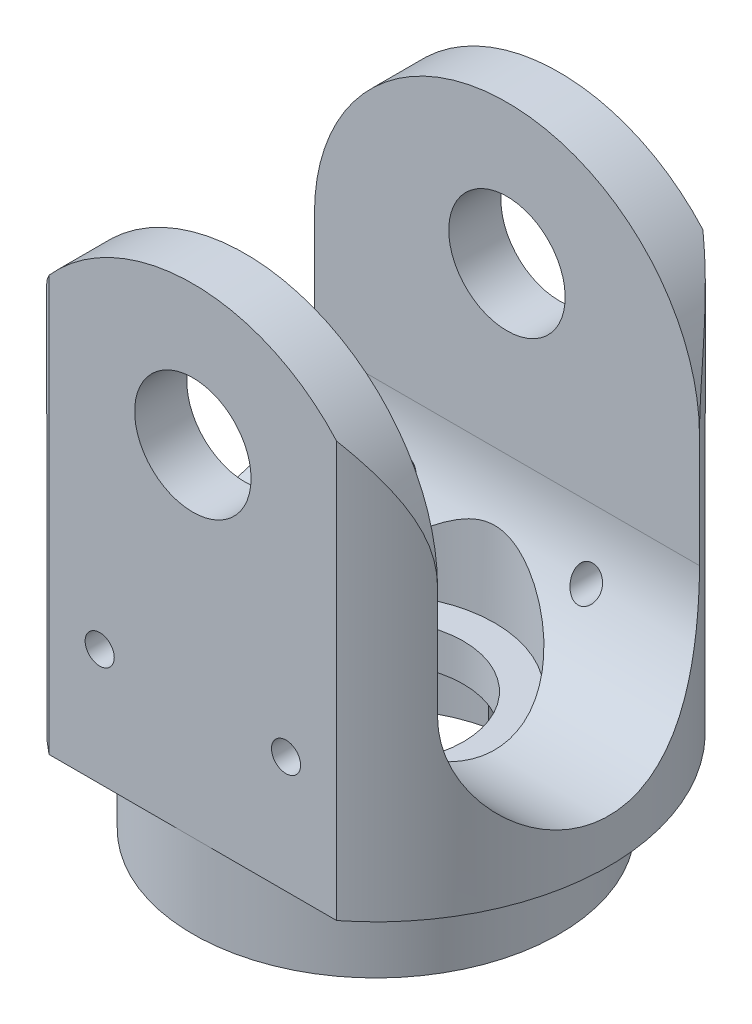
SolidWorks part; units mm, degrees
material "7075-T6 (SN)"
ref_plane "X-Y Datum" through (0, 0, 0) normal (0, 0, 1) x (1, 0, 0)
ref_plane "X-Z Datum" through (0, 0, 0) normal (0, 1, 0) x (1, 0, 0)
ref_plane "Y-Z Datum" through (0, 0, 0) normal (1, 0, 0) x (0, 0, -1)
sketch "Sketch1" plane through (0, 0, 0) normal (0, 1, 0) x (1, 0, 0)
  circle A0 centre (0, 0) radius 12.7
  dimension "D1" = 25.4
extrude "Boss-Extrude1" add sketch "Sketch1" along normal blind 15.367 and the other way blind 15.367
ref_plane "Plane2" through (0, 0, 9.9886) normal (0, 0, 1) x (1, 0, 0)
sketch "Sketch4" plane through (0, 0, 9.9886) normal (0, 0, 1) x (1, 0, 0)
  line L1 (-12.7, 15.367) -> (12.7, 15.367)
  line L2 (-12.7, 15.367) -> (-12.7, -15.367)
  line L3 (-12.7, -15.367) -> (12.7, -15.367)
  line L4 (12.7, 15.367) -> (12.7, -15.367)
extrude "Cut-Extrude2" cut sketch "Sketch4" along normal through all
mirror "Mirror2" about plane through (0, 0, 0) normal (0, 0, 1) of "Cut-Extrude2"
sketch "Sketch5" plane through (0, 0, 0) normal (1, 0, 0) x (0, 0, -1)
  line L0 (9.9886, 15.367) -> (-9.9886, 15.367) construction
  line L1 (-7.1437, 15.367) -> (7.1437, 15.367)
  line L2 (-7.1437, 15.367) -> (-7.1437, -1.27)
  line L3 (-7.1437, -1.27) -> (7.1438, -1.27)
  line L4 (7.1437, 15.367) -> (7.1438, -1.27)
  line L5 (0, 13.97) -> (0, -13.97) construction
  line L6 (0, -8.4138) -> (0, 15.367) construction
  arc A0 (-7.1437, -1.27) -> (7.1438, -1.27) centre (0, -1.27) ccw
  dimension "D3" = 16.637
  dimension "D4" = 23.7808
  dimension "D1" = 14.2875
  dimension "D2" = 7.1437
extrude "Cut-Extrude3" cut sketch "Sketch5" against normal through all both and the other way through all contours L6 A0 L3 | A0 L6 L3 | L2 L1 L4 L3 region at (0, -4.3019, 3.0319) region at (0, -4.3019, -3.0319)
sketch "Sketch6" plane through (0, 0, 9.9886) normal (0, 0, 1) x (1, 0, 0)
  line L0 (0, -43.0151) -> (0, 43.0151) construction
  line L1 (-7.8434, 15.367) -> (7.8434, 15.367) construction
  line L2 (10.5004, 4.8666) -> (14.8497, 4.8666)
  line L3 (-10.5004, 4.8666) -> (-14.8497, 4.8666)
  circle A0 centre (0, 4.8666) radius 10.5004
  arc A1 (14.8497, 4.8666) -> (-14.8497, 4.8666) centre (0, 4.8666) ccw
  line M2 (7.8434, 15.367) -> (-7.8434, 15.367)
  line M3 (-7.8434, 15.367) -> (-7.8434, -15.367)
  line M5 (7.8434, -15.367) -> (7.8434, 15.367)
  dimension "D1" = 21.0007
extrude "Cut-Extrude4" cut sketch "Sketch6" against normal through all contours L2 A1 L3 A0 M3 M2 M5 | A0 M2 M3 | A0 M5 M2 region at (10.124, 8.7197, 9.9886) region at (5.9543, 14.3505, 9.9886) region at (-5.9543, 14.3505, 9.9886)
sketch "Sketch7" plane through (0, -15.367, 0) normal (0, -1, 0) x (1, 0, 0)
  circle A0 centre (0, 0) radius 4.7625
  dimension "D1" = 9.525
extrude "Cut-Extrude5" cut sketch "Sketch7" against normal through all
sketch "Sketch9" plane through (0, -15.367, 0) normal (0, -1, 0) x (1, 0, 0)
  circle A0 centre (0, 0) radius 9.9822
  circle A1 centre (0, 0) radius 17.8528
  dimension "D1" = 19.9644
extrude "Cut-Extrude6" cut sketch "Sketch9" against normal blind 4.572
ref_plane "Plane3" through (0, 15.367, 0) normal (0, 1, 0) x (1, 0, 0)
sketch "Sketch10" plane through (0, 15.367, 0) normal (0, 1, 0) x (1, 0, 0)
  circle A0 centre (0, 0) radius 6.477
  dimension "D1" = 12.954
extrude "Cut-Extrude7" cut sketch "Sketch10" against normal blind 24.257
sketch "Sketch11" plane through (0, 0, 9.9886) normal (0, 0, 1) x (1, 0, 0)
  line L0 (-9.9822, -10.795) -> (9.9822, -10.795) construction
  line L1 (0, 7.747) -> (0, 0) construction
  circle A0 centre (0, 7.747) radius 3.175
  dimension "D1" = 6.35
  dimension "D2" = 18.542
extrude "Cut-Extrude8" cut sketch "Sketch11" against normal through all
sketch "Sketch12" plane through (0, 0, -9.9886) normal (0, 0, -1) x (-1, 0, 0)
  line L0 (-7.8434, -10.795) -> (7.8434, -10.795) construction
  line L1 (7.8434, 11.848) -> (7.8434, -10.795) construction
  line L2 (-7.8434, -10.795) -> (-7.8434, 11.848) construction
  circle A0 centre (5.0811, -4.445) radius 0.7938
  circle A1 centre (-5.0811, -4.445) radius 0.7938
  point P6 (-5.8749, -4.445)
  point P7 (5.8749, -4.445)
  dimension "D1" = 1.5875
  dimension "D2" = 1.5875
  dimension "D3" = 6.35
  dimension "D4" = 6.35
  dimension "D5" = 1.9685
  dimension "D6" = 1.9685
extrude "Cut-Extrude9" cut sketch "Sketch12" against normal through all both and the other way through all
sketch "Sketch13" plane through (0, -15.367, 0) normal (0, -1, 0) x (1, 0, 0)
  line L0 (-0.2399, -7.9974) -> (7.5971, -2.5099)
  line L1 (4.5892, -6.554) -> (0, 0) construction
  line L2 (-2.54, 0) -> (2.54, 0)
  circle A0 centre (0, 0) radius 8.001
  circle M5 centre (0, 0) radius 4.7625
  dimension "D1" = 16.002
  dimension "D2" = 35
  dimension "D3" = 6.4135
  dimension "D4" = 5.08
extrude "Cut-Extrude10" [suppressed] cut sketch "Sketch13" against normal blind 4.445 contours L0 A0 M5
sketch "Sketch14" [suppressed] plane through (0, -15.367, 0) normal (0, -1, 0) x (1, 0, 0)
  line L0 (0, 0) -> (-0.2399, -7.9974) construction
  line L1 (0, 0) -> (7.5971, -2.5099) construction
  circle A0 centre (-0.217, -7.2354) radius 1.5875
  circle A1 centre (6.8736, -2.2708) radius 1.5875
  dimension "D1" = 3.175
  dimension "D2" = 3.175
  dimension "D3" = 0.762
  dimension "D4" = 0.762
extrude "Cut-Extrude11" [suppressed] cut sketch "Sketch14" against normal up to surface (4.445 mm away)
sketch "Sketch15" plane through (0, -15.367, 0) normal (0, -1, 0) x (1, 0, 0)
  line L0 (-0.2399, -7.9974) -> (7.5971, -2.5099)
  line L1 (4.5892, -6.554) -> (0, 0) construction
  line L2 (-1.905, 0) -> (1.905, 0)
  circle A1 centre (0, 0) radius 9.9822 construction
  circle A2 centre (0, 0) radius 8.001
  circle M4 centre (0, 0) radius 4.7625
  dimension "D3" = 16.002
  dimension "D1" = 35
  dimension "D2" = 6.4135
  dimension "D4" = 3.81
extrude "Cut-Extrude12" cut sketch "Sketch15" against normal blind 4.445 contours A2 M4 region at (-5.4145, -15.367, 5.5794)
sketch "Sketch16" plane through (0, -15.367, 0) normal (0, -1, 0) x (1, 0, 0)
  line L0 (0, 0) -> (-0.2399, -7.9974) construction
  line L1 (0, 0) -> (7.5971, -2.5099) construction
  circle A4 centre (-0.217, -7.2354) radius 1.5875
  circle A5 centre (6.8736, -2.2708) radius 1.5875
  dimension "D1" = 3.175
  dimension "D4" = 0.762
  dimension "D2" = 3.175
  dimension "D3" = 0.762
extrude "Cut-Extrude13" cut sketch "Sketch16" against normal up to surface (4.445 mm away) up to face at (0, -10.922, -4.7625)
sketch "Pick Up Point" plane through (0, 0, 0) normal (0, 0, 1) x (1, 0, 0)
  point P0 (0, 7.747)
ref_plane "Plane4" through (0, 15.367, -7.1437) normal (0, 1, 0) x (1, 0, 0)
sketch "Sketch20" plane through (0, 15.367, -7.1437) normal (0, 1, 0) x (1, 0, 0)
  circle A0 centre (0, -7.1437) radius 12.7
  point P3 (0, 5.5562)
  point P4 (0, -19.8438)
  point P6 (0, -7.1437)
  dimension "D1" = 25.4
ref_plane "Plane5" through (0, -15.367, 0) normal (0, -1, 0) x (-1, 0, 0)
sketch "Sketch21" plane through (0, -15.367, 0) normal (0, -1, 0) x (-1, 0, 0)
  point P0 (0, 0)
ref_point "Point1"
ref_point "Point2"
ref_point "Point3"
ref_point "Point4"
ref_point "Point5"
ref_axis "Axis1" [suppressed] through (0, -8.89, 0) along (0, -1, 0)
sketch "Sketch22" plane through (0, 0, 9.9886) normal (0, 0, 1) x (1, 0, 0)
  arc A0 (7.8434, 11.848) -> (-7.8434, 11.848) centre (0, 4.8666) ccw construction
  point P0 (0, 15.367)
sketch "Sketch23" plane through (0, -10.922, 0) normal (0, -1, 0) x (1, 0, 0)
  line L0 (-1.693, -7.8198) -> (7.9273, -1.0834)
  arc A0 (7.9273, -1.0834) -> (-1.693, -7.8198) centre (0, 0) ccw
sketch3d "3DSketch1"
  line L0 (0, 7.747, 9.9886) -> (0, 7.747, -9.9886) construction
  line L3 (0, 7.747, 7.1437) -> (0, 7.747, 9.9886) construction
  line L4 (0, 7.747, -9.9886) -> (0, 7.747, -7.1438) construction
  point P6 (0, 7.747, 0)
